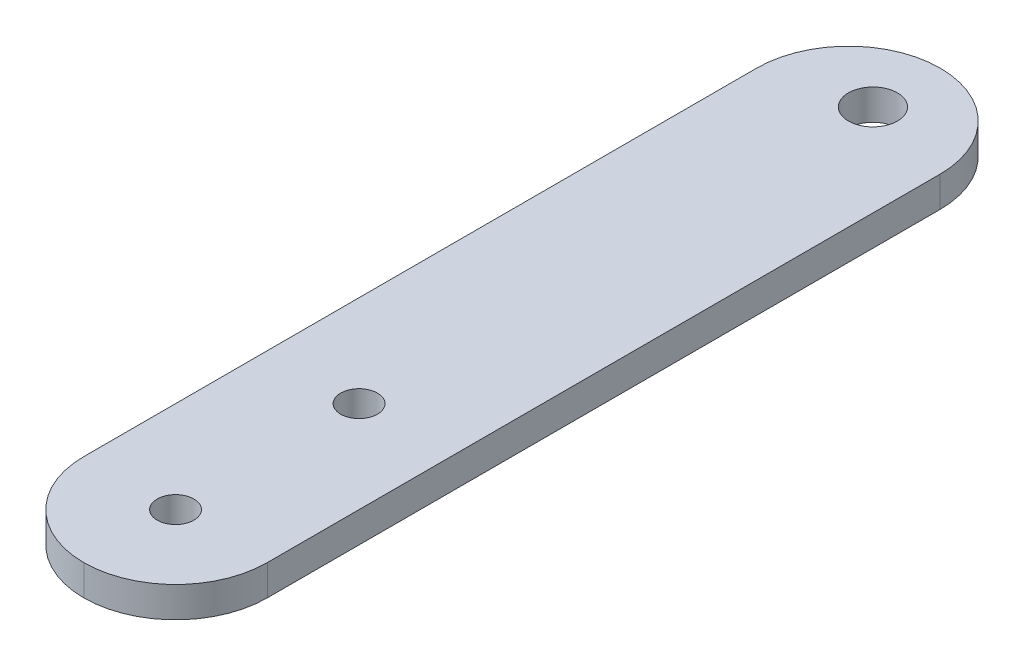
SolidWorks part; units mm, degrees
ref_plane "Plan de face" through (0, 0, 0) normal (0, 0, 1) x (1, 0, 0)
ref_plane "Plan de dessus" through (0, 0, 0) normal (0, 1, 0) x (1, 0, 0)
ref_plane "Plan de droite" through (0, 0, 0) normal (1, 0, 0) x (0, 0, -1)
sketch "Esquisse1" plane through (0, 0, 0) normal (0, 0, 1) x (1, 0, 0)
  line L1 (-7.5, -1.25) -> (7.5, -1.25)
  line L2 (-7.5, -1.25) -> (-7.5, 1.25)
  line L3 (-7.5, 1.25) -> (7.5, 1.25)
  line L4 (7.5, -1.25) -> (7.5, 1.25)
  line L5 (-7.5, -1.25) -> (7.5, 1.25) construction
  line L6 (-7.5, 1.25) -> (7.5, -1.25) construction
  point P0 (0, 0)
  dimension "D1" = 15
  dimension "D2" = 2.5
extrude "Extrusion1" add sketch "Esquisse1" along normal blind 70
fillet "Congé1" radius 7.5 2 edges at (-7.5, 0, 70) (7.5, 0, 70)
sketch "Esquisse2" plane through (0, 1.25, 0) normal (0, 1, 0) x (1, 0, 0)
  circle A0 centre (0, -62.5) radius 1.5
  arc A3 (-7.5, -62.5) -> (0, -70) centre (0, -62.5) ccw construction
  dimension "D2" = 3
extrude "Extrusion2" cut sketch "Esquisse2" against normal through all
sketch "Esquisse3" plane through (0, 1.25, 0) normal (0, 1, 0) x (1, 0, 0)
  circle A0 centre (0, -5.5) radius 2
  circle A1 centre (0, -62.5) radius 1.5 construction
  dimension "D1" = 4
  dimension "D2" = 57
extrude "Extrusion3" cut sketch "Esquisse3" against normal through all
fillet "Congé2" radius 7.5 2 edges at (7.5, 0, 0) (-7.5, 0, 0)
sketch "Esquisse4" plane through (0, 1.25, 0) normal (0, 1, 0) x (1, 0, 0)
  circle A0 centre (0, -47.5) radius 1.5
  circle A1 centre (0, -62.5) radius 1.5 construction
  dimension "D1" = 3
  dimension "D2" = 15
extrude "Extrusion4" cut sketch "Esquisse4" against normal through all
